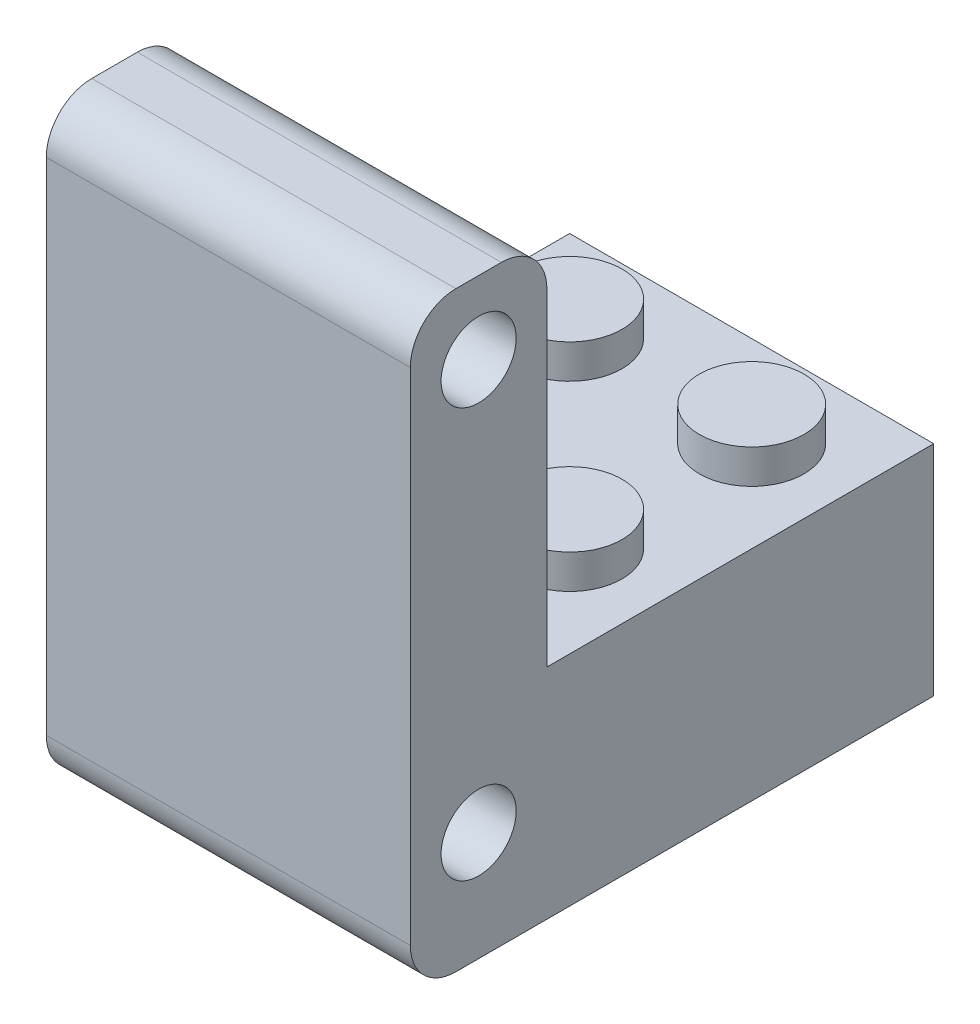
SolidWorks part; units mm, degrees
ref_plane "Front Plane" through (0, 0, 0) normal (0, 0, 1) x (1, 0, 0)
ref_plane "Top Plane" through (0, 0, 0) normal (0, 1, 0) x (1, 0, 0)
ref_plane "Right Plane" through (0, 0, 0) normal (1, 0, 0) x (0, 0, -1)
sketch "Sketch1" plane through (76, 0, 0) normal (1, 0, 0) x (0, 0, -1)
  line L0 (-39.3671, -19.7967) -> (-39.3671, -29.3967) construction
  line L1 (-39.3671, -19.7967) -> (-39.3671, -29.3967) construction
  line L2 (-39.3671, -29.3967) -> (-62.3671, -29.3967)
  line L3 (-62.3671, -29.3967) -> (-62.3671, -3.3967)
  line L4 (-62.3671, -3.3967) -> (-56.3671, -3.3967)
  line L5 (-56.3671, -3.3967) -> (-56.3671, -19.7967)
  line L6 (-56.3671, -19.7967) -> (-39.3671, -19.7967)
  line L7 (-39.3671, -19.7967) -> (-39.3671, -29.3967)
  arc A0 (-59.3671, -25.9217) -> (-59.3671, -23.2717) centre (-59.3671, -24.5967) ccw construction
  arc A1 (-59.3671, -7.9217) -> (-59.3671, -5.2717) centre (-59.3671, -6.5967) ccw construction
  arc A2 (-59.3671, -25.9217) -> (-59.3671, -23.2717) centre (-59.3671, -24.5967) ccw construction
  arc A3 (-59.3671, -7.9217) -> (-59.3671, -5.2717) centre (-59.3671, -6.5967) ccw construction
  circle A4 centre (-59.3671, -24.5967) radius 1.65
  circle A5 centre (-59.3671, -6.5967) radius 1.65
  dimension "D4" = 3.3
  dimension "D1" = 6
  dimension "D2" = 17
  dimension "D3" = 26
extrude "Boss-Extrude1" add sketch "Sketch1" against normal blind 16
sketch "Sketch2" plane through (0, -19.7967, 0) normal (0, 1, 0) x (1, 0, 0)
  line L4 (76, -56.3671) -> (76, -39.3671)
  line L5 (76, -39.3671) -> (60, -39.3671)
  line L6 (60, -39.3671) -> (60, -56.3671)
  line L7 (60, -56.3671) -> (76, -56.3671)
  line L8 (76, -56.3671) -> (76, -39.3671)
  line L9 (76, -39.3671) -> (60, -39.3671)
  line L10 (60, -39.3671) -> (60, -56.3671)
  line L11 (60, -56.3671) -> (76, -56.3671)
  circle A0 centre (64, -43.3671) radius 2.3
  circle A1 centre (72, -43.3671) radius 2.3
  circle A2 centre (72, -51.3671) radius 2.3
  circle A3 centre (64, -51.3671) radius 2.3
  circle A4 centre (64, -35.3671) radius 2.4 construction
  circle A5 centre (72, -35.3671) radius 2.4 construction
  circle A6 centre (64, -35.3671) radius 2.4
  circle A7 centre (72, -35.3671) radius 2.4
  point P18 (0, 0)
  point P19 (0, 0)
  point P20 (0, 0)
  point P21 (0, 0)
  point P22 (0, 0)
  point P23 (0, 0)
  point P24 (0, 0)
  dimension "D4" = 4.6
  dimension "D2" = 8
  dimension "D3" = 8
  dimension "D1" = 0
extrude "Boss-Extrude2" add sketch "Sketch2" along normal blind 1.5 contours A3 | A0 | A1 | A2 region at (64, -19.7967, 43.3671) region at (72, -19.7967, 43.3671) region at (72, -19.7967, 51.3671) region at (64, -19.7967, 51.3671)
fillet "Fillet1" radius 2 3 edges at (68, -29.3967, 62.3671) (68, -3.3967, 62.3671) (68, -3.3967, 56.3671)
